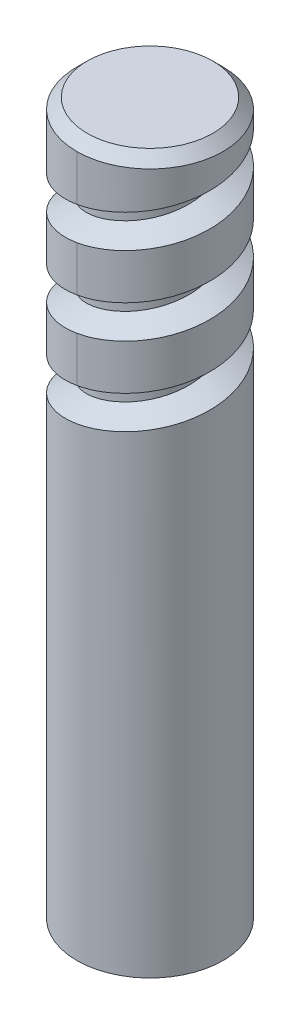
SolidWorks part; units mm, degrees
ref_plane "Plano frontal" through (0, 0, 0) normal (0, 0, 1) x (1, 0, 0)
ref_plane "Plano superior" through (0, 0, 0) normal (0, 1, 0) x (1, 0, 0)
ref_plane "Plano direito" through (0, 0, 0) normal (1, 0, 0) x (0, 0, -1)
sketch "Esboço1" plane through (0, 0, 0) normal (0, 0, 1) x (1, 0, 0)
  line L0 (4.7385, -110.9617) -> (-2.2615, -110.9617)
  line L1 (4.7385, -110.9617) -> (4.7385, -42.9617)
  line L2 (4.7385, -42.9617) -> (-2.2615, -42.9617)
  line L3 (-2.2615, -110.9617) -> (-2.2615, -42.9617)
  point P4 (0, 0)
  dimension "D1" = 7
  dimension "D2" = 68
sketch "Esboço2" plane through (0, 0, 0) normal (1, 0, 0) x (0, 0, -1)
  line L0 (1, -17) -> (-6, -17)
  line L1 (1, -17) -> (1, 51)
  line L2 (1, 51) -> (-6, 51)
  line L3 (-6, -17) -> (-6, 51)
  dimension "D1" = 7
  dimension "D2" = 68
revolve "Revolução2" add sketch "Esboço2" angle 360 about L3 reverse direction yes
sketch "Esboço3" plane through (0, 51, 0) normal (0, 1, 0) x (1, 0, 0)
  line L0 (0, -13) -> (0, -6)
  line L1 (0, -13) -> (0, -12.6859)
  line L2 (0, -12.6859) -> (0, -13)
  line L3 (0, -13) -> (1.2547, -16.4539)
  circle A0 centre (0, -6) radius 7 construction
  point P7 (-45009.9436, -500000)
  point P8 (0, 0)
chamfer "Chanfro1" distance 1 angle 45 1 edges at (0, 51, 13)
thread "Rosca2" pitch 3.6286 method cut profile "Perfil da rosca2" start angle 60, offset 0, length 22.5, pitch 7.5, diameter 14
ref_plane "Plano3" through (-3.5, 50, -0.0622) normal (-0.866, 0, 0.5) x (-0.5, 0, -0.866)
sketch "Perfil da rosca2" plane through (-3.5, 50, -0.0622) normal (-0.866, 0, 0.5) x (-0.5, 0, -0.866)
  line L0 (0, 0) -> (0, 3.6286) construction
  line L11 (0, 0) -> (0, 3.175)
  line L12 (0, 3.175) -> (-1.964, 2.0411)
  line L13 (-1.964, 2.0411) -> (-1.964, 1.1339)
  line L15 (-1.964, 1.1339) -> (0, 0)
  line L17 (-1.964, 1.5875) -> (0, 1.5875) construction
  point P2 (0, 0)
  dimension "Pitch" = 3.6286
  dimension "Profile_Angle" = 60
  dimension "Profile_Land" = 0.9071
  dimension "Profile_Height" = 1.964
